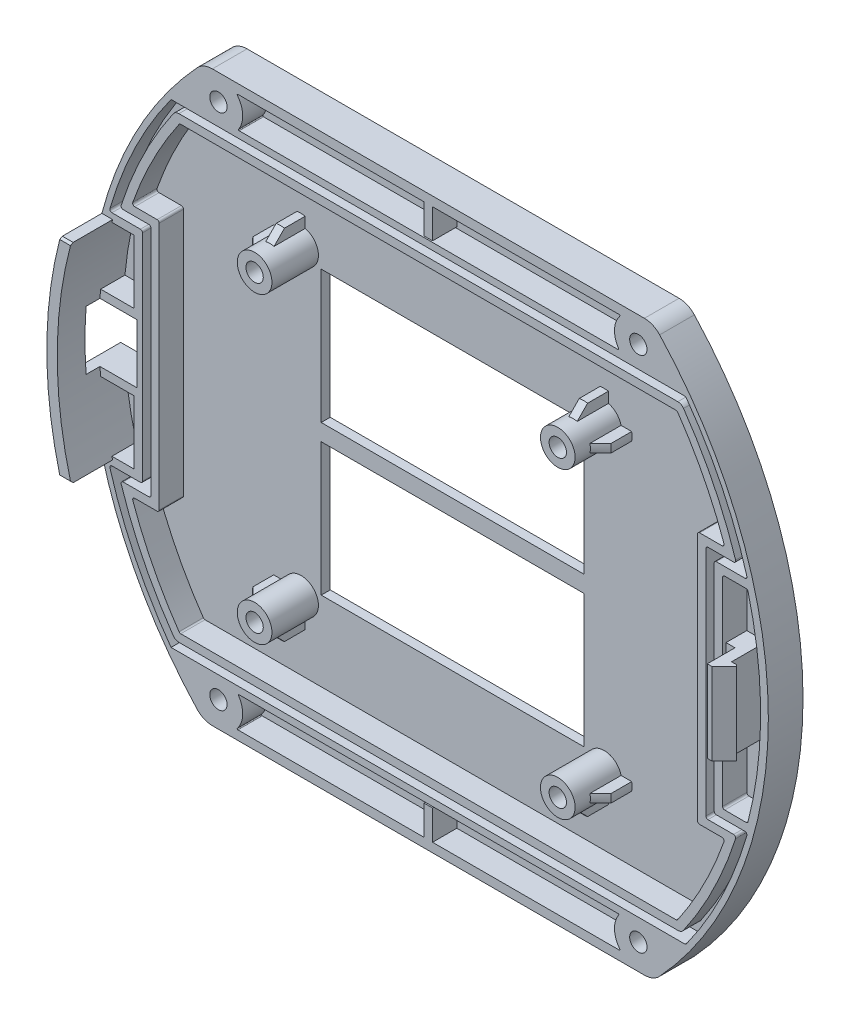
SolidWorks part; units mm, degrees
ref_plane "Front Plane" through (0, 0, 0) normal (0, 0, 1) x (1, 0, 0)
ref_plane "Top Plane" through (0, 0, 0) normal (0, 1, 0) x (1, 0, 0)
ref_plane "Right Plane" through (0, 0, 0) normal (1, 0, 0) x (0, 0, -1)
sketch "Sketch1" plane through (0, 0, 0) normal (0, 0, 1) x (1, 0, 0)
  line L0 (0, 35) -> (0, -35) construction
  line L7 (-37.5, -35) -> (37.5, -35)
  line L8 (37.5, 35) -> (-37.5, 35)
  line L10 (37.5, 35) -> (37.5, -35) construction
  line L11 (-37.5, 35) -> (-37.5, -35) construction
  arc A4 (-37.5, 35) -> (-37.5, -35) centre (10, 0) ccw
  arc A5 (37.5, 35) -> (37.5, -35) centre (-10, 0) cw
  point P17 (10, 0)
  dimension "D2" = 75
extrude "Boss-Extrude1" add sketch "Sketch1" along normal blind 5
sketch "Sketch2" plane through (0, 0, 5) normal (0, 0, 1) x (1, 0, 0)
  line L0 (-49.0021, 0) -> (49.0021, 0) construction
  line L1 (-42.635, 0) -> (-42.635, -15) construction
  line L2 (-42.635, 0) -> (-42.635, 15) construction
  line L3 (-45.5112, 15) -> (-47.0636, 15)
  line L4 (-45.5112, -15) -> (-47.0636, -15)
  arc A0 (-37.5, 35) -> (-37.5, -35) centre (10, 0) ccw construction
  arc A1 (37.5, -35) -> (37.5, 35) centre (-10, 0) ccw construction
  arc A2 (-47.0636, 15) -> (-47.0636, -15) centre (10, 0) ccw
  arc A4 (-36.2924, 34.1102) -> (-36.2924, -34.1102) centre (10, 0) ccw
  arc A5 (-45.5112, 15) -> (-45.5112, -15) centre (10, 0) ccw
  dimension "D1" = 15
  dimension "D2" = 15
  dimension "D3" = 1.5
extrude "Boss-Extrude2" add sketch "Sketch2" along normal blind 6
ref_plane "Plane2" through (-42, 0, 0) normal (1, 0, 0) x (0, 0, -1)
sketch "Sketch6" plane through (-42, 0, 0) normal (1, 0, 0) x (0, 0, -1)
  line L0 (0, 0) -> (-11, 0) construction
  line L1 (-11, 15) -> (-11, -15) construction
  line L2 (-11, 0) -> (-7, 0) construction
  line L3 (-7, 0) -> (-7, 4.25)
  line L4 (-7, 0) -> (-7, -4.25)
  line L5 (-7, 4.25) -> (0, 4.25)
  line L6 (0, -35) -> (0, 35) construction
  line L7 (0, 4.25) -> (0, -4.25)
  line L8 (0, -4.25) -> (-7, -4.25)
  dimension "D1" = 4
  dimension "D2" = 4.25
  dimension "D3" = 4.25
extrude "Cut-Extrude2" cut sketch "Sketch6" against normal blind 8
sketch "Sketch8" plane through (0, 0, 5) normal (0, 0, 1) x (1, 0, 0)
  line L0 (0, 0) -> (0, 35) construction
  line L1 (37.5, 35) -> (-37.5, 35) construction
  line L2 (0, 35) -> (0, -35) construction
  line L3 (-37.5, -35) -> (37.5, -35) construction
  line L4 (0, 0) -> (49.0021, 0) construction
  line L5 (0, 0) -> (42, 0) construction
  line L6 (42, 0) -> (44, 0) construction
  line L13 (0, 0) -> (43.2, 0) construction
  line L14 (43.7, -5.9) -> (45.2, -5.9)
  line L15 (45.2, -5.9) -> (45.2, 5.9)
  line L16 (45.2, 5.9) -> (43.7, 5.9)
  line L19 (45.2, 5.9) -> (43.7, 5.9) construction
  line L20 (43.7, 5.9) -> (43.7, -5.9)
  arc A0 (37.5, -35) -> (37.5, 35) centre (-10, 0) ccw construction
  point P5 (45.2, 0)
  dimension "D1" = 42
  dimension "D2" = 2
  dimension "D3" = 11.8
  dimension "D5" = 1.5
  dimension "D6" = 43.2
extrude "Boss-Extrude4" add sketch "Sketch8" along normal blind 3.5
ref_plane "Plane3" through (0, 0, 6.5) normal (0, 0, 1) x (1, 0, 0)
sketch "Sketch9" plane through (0, 0, 6.5) normal (0, 0, 1) x (1, 0, 0)
  line L0 (45.2, 5.9) -> (46.4, 5.9)
  line L1 (46.4, 5.9) -> (46.4, -5.9)
  line L2 (46.4, -5.9) -> (45.2, -5.9)
  line L3 (45.2, 5.9) -> (45.2, -5.9)
  dimension "D1" = 1.2
extrude "Boss-Extrude5" add sketch "Sketch9" along normal blind 2
chamfer "Chamfer2" distance 2 angle 45 1 edges at (46.4, 0, 8.5)
chamfer "Chamfer3" distance 0.5 angle 45 1 edges at (46.4, 0, 6.5)
sketch "Sketch10" plane through (0, 0, 0) normal (0, 0, 1) x (1, 0, 0)
  line L0 (-32.4294, 41) -> (32.4294, 41)
  line L1 (-37.5, 35) -> (37.5, 35)
  line L2 (-32.4294, -41) -> (32.4294, -41)
  line L3 (-37.5, -35) -> (37.5, -35)
  line L4 (0, 41) -> (0, -41) construction
  line L5 (-10, 0) -> (10, 0) construction
  arc A0 (-37.5, 35) -> (-32.4294, 41) centre (10, 0) cw
  arc A1 (37.5, 35) -> (32.4294, 41) centre (-10, 0) ccw
  arc A2 (-37.5, -35) -> (-32.4294, -41) centre (10, 0) ccw
  arc A3 (37.5, -35) -> (32.4294, -41) centre (-10, 0) cw
extrude "Boss-Extrude6" add sketch "Sketch10" along normal blind 5
sketch "Sketch11" plane through (0, 0, 5) normal (0, 0, 1) x (1, 0, 0)
  line L0 (-41.2021, 0) -> (42.0021, 0) construction
  line L1 (0, 41) -> (0, -41) construction
  circle A0 centre (-30.2641, -37.3072) radius 1.25
  circle A1 centre (30.2641, -37.3072) radius 1.25
  circle A2 centre (30.2641, 37.3072) radius 1.25
  circle A3 centre (-30.2641, 37.3072) radius 1.25
extrude "Cut-Extrude3" cut sketch "Sketch11" against normal blind 5
sketch "Sketch12" plane through (0, 0, 0) normal (0, 0, -1) x (-1, 0, 0)
  circle A0 centre (-30.2641, 37.3072) radius 3
  circle A1 centre (30.2641, 37.3072) radius 3
  circle A2 centre (30.2641, -37.3072) radius 3
  circle A3 centre (-30.2641, -37.3072) radius 3
  dimension "D1" = 6
  dimension "D2" = 6
  dimension "D3" = 6
  dimension "D4" = 6
extrude "Cut-Extrude4" cut sketch "Sketch12" against normal blind 2.5
sketch "Sketch13" plane through (0, 0, 5) normal (0, 0, 1) x (1, 0, 0)
  line L0 (-46.0165, 15.8) -> (-41.2021, 15.8)
  line L1 (-41.2021, 15.8) -> (-41.2021, -15.8)
  line L2 (-41.2021, -15.8) -> (-46.0165, -15.8)
  line L3 (-37.094, -34.2) -> (37.094, -34.2)
  line L4 (46.0165, -15.8) -> (41.2021, -15.8)
  line L5 (41.2021, -15.8) -> (41.2021, 15.8)
  line L6 (41.2021, 15.8) -> (46.0165, 15.8)
  line L7 (37.094, 34.2) -> (-37.094, 34.2)
  line L8 (10, 0) -> (-10, 0) construction
  line L9 (0, 34.2) -> (0, -34.2) construction
  line L10 (-44.4081, 17) -> (-40.0021, 17)
  line L11 (-35.9591, 33) -> (35.9591, 33)
  line L12 (-40.0021, 17) -> (-40.0021, -17)
  line L13 (44.4081, 17) -> (40.0021, 17)
  line L14 (40.0021, 17) -> (40.0021, -17)
  line L15 (44.4081, -17) -> (40.0021, -17)
  line L16 (-35.9591, -33) -> (35.9591, -33)
  line L17 (-44.4081, -17) -> (-40.0021, -17)
  line L18 (0, 33) -> (0, -33) construction
  arc A0 (-37.094, 34.2) -> (-46.0165, 15.8) centre (10, 0) ccw
  arc A1 (-46.0165, -15.8) -> (-37.094, -34.2) centre (10, 0) ccw
  arc A2 (37.094, -34.2) -> (46.0165, -15.8) centre (-10, 0) ccw
  arc A3 (46.0165, 15.8) -> (37.094, 34.2) centre (-10, 0) ccw
  arc A4 (-36.7797, 32.5714) -> (-44.4081, 17) centre (10, 0) ccw
  arc A5 (-36.7797, 32.5714) -> (-35.9591, 33) centre (-35.9591, 32) cw
  arc A6 (36.7797, 32.5714) -> (35.9591, 33) centre (35.9591, 32) ccw
  arc A7 (36.7797, 32.5714) -> (44.4081, 17) centre (-10, 0) cw
  arc A8 (36.7797, -32.5714) -> (44.4081, -17) centre (-10, 0) ccw
  arc A9 (36.7797, -32.5714) -> (35.9591, -33) centre (35.9591, -32) cw
  arc A10 (-36.7797, -32.5714) -> (-35.9591, -33) centre (-35.9591, -32) ccw
  arc A11 (-36.7797, -32.5714) -> (-44.4081, -17) centre (10, 0) cw
  point P23 (0, 33)
  point P28 (40.0021, 0)
  point P42 (-40.0021, 0)
  point P45 (0, 0)
extrude "Cut-Extrude6" cut sketch "Sketch13" against normal blind 2.5
sketch "Sketch14" plane through (0, 0, 5) normal (0, 0, 1) x (1, 0, 0)
  line L16 (-42.7507, 18.2) -> (-38.8021, 18.2)
  line L17 (-38.8021, 18.2) -> (-38.8021, -18.2)
  line L18 (-38.8021, -18.2) -> (-42.7507, -18.2)
  line L19 (-35.8545, -31.8) -> (35.8545, -31.8)
  line L20 (42.7507, -18.2) -> (38.8021, -18.2)
  line L21 (38.8021, -18.2) -> (38.8021, 18.2)
  line L22 (38.8021, 18.2) -> (42.7507, 18.2)
  line L23 (35.8545, 31.8) -> (-35.8545, 31.8)
  line L24 (-42.7507, 18.2) -> (-38.8021, 18.2)
  line L25 (-38.8021, 18.2) -> (-38.8021, -18.2)
  line L26 (-38.8021, -18.2) -> (-42.7507, -18.2)
  line L27 (-35.8545, -31.8) -> (35.8545, -31.8)
  line L28 (42.7507, -18.2) -> (38.8021, -18.2)
  line L29 (38.8021, -18.2) -> (38.8021, 18.2)
  line L30 (38.8021, 18.2) -> (42.7507, 18.2)
  line L31 (35.8545, 31.8) -> (-35.8545, 31.8)
  arc A16 (-35.8545, 31.8) -> (-42.7507, 18.2) centre (10, 0) ccw
  arc A17 (-42.7507, -18.2) -> (-35.8545, -31.8) centre (10, 0) ccw
  arc A18 (35.8545, -31.8) -> (42.7507, -18.2) centre (-10, 0) ccw
  arc A19 (42.7507, 18.2) -> (35.8545, 31.8) centre (-10, 0) ccw
  arc A20 (-35.8545, 31.8) -> (-42.7507, 18.2) centre (10, 0) ccw
  arc A21 (-42.7507, -18.2) -> (-35.8545, -31.8) centre (10, 0) ccw
  arc A22 (35.8545, -31.8) -> (42.7507, -18.2) centre (-10, 0) ccw
  arc A23 (42.7507, 18.2) -> (35.8545, 31.8) centre (-10, 0) ccw
  dimension "D1" = 1.2
extrude "Cut-Extrude7" cut sketch "Sketch14" against normal blind 3.5
sketch "Sketch15" plane through (0, 0, 5) normal (0, 0, 1) x (1, 0, 0)
  line L0 (0.031, 41) -> (0.031, -41) construction
  line L1 (-40.0021, -0.0076) -> (42.0021, -0.0076) construction
  line L2 (27.5192, -39.6767) -> (-27.4573, -39.6767)
  line L3 (-27.2755, 35.2002) -> (27.3374, 35.2002)
  line L4 (-27.2831, -35.2042) -> (27.345, -35.2042)
  line L5 (27.5155, 39.6568) -> (-27.4535, 39.6568)
  arc A12 (-27.5316, 39.4943) -> (-27.3585, 35.356) centre (-30.2641, 37.3072) cw
  arc A13 (27.5935, 39.4943) -> (27.4204, 35.356) centre (30.326, 37.3072) ccw
  arc A14 (27.5972, -39.5141) -> (27.4278, -35.3603) centre (30.326, -37.3225) cw
  arc A15 (-27.5352, -39.5141) -> (-27.3659, -35.3603) centre (-30.2641, -37.3225) ccw
  arc A16 (-27.2755, 35.2002) -> (-27.3585, 35.356) centre (-27.2755, 35.3002) cw
  arc A17 (-27.5316, 39.4943) -> (-27.4535, 39.6568) centre (-27.4535, 39.5568) cw
  arc A18 (27.4278, -35.3603) -> (27.345, -35.2042) centre (27.345, -35.3042) ccw
  arc A19 (27.3374, 35.2002) -> (27.4204, 35.356) centre (27.3374, 35.3002) ccw
  arc A20 (27.5935, 39.4943) -> (27.5155, 39.6568) centre (27.5155, 39.5568) ccw
  arc A21 (27.5192, -39.6767) -> (27.5972, -39.5141) centre (27.5192, -39.5767) ccw
  arc A22 (-27.3659, -35.3603) -> (-27.2831, -35.2042) centre (-27.2831, -35.3042) cw
  arc A23 (-27.5352, -39.5141) -> (-27.4573, -39.6767) centre (-27.4573, -39.5767) ccw
  point P14 (0.031, -39.6767)
  point P20 (0.031, -35.2042)
  dimension "D1" = 3.5
  dimension "D2" = 0.1
  dimension "D3" = 0.1
  dimension "D4" = 0.1
  dimension "D5" = 0.1
  dimension "D6" = 0.1
extrude "Cut-Extrude8" cut sketch "Sketch15" against normal blind 3.5
sketch "Sketch16" plane through (0, 0, 5) normal (0, 0, 1) x (1, 0, 0)
  line L2 (42.4021, -15.8) -> (42.4021, 15.8)
  line L3 (42.4021, -14.6) -> (42.4021, 14.6)
  line L5 (41.2021, 14.6) -> (46.0165, 14.6)
  line L6 (42.4021, 14.6) -> (46.0165, 14.6)
  line L8 (46.0165, -14.6) -> (41.2021, -14.6)
  line L9 (46.0165, -14.6) -> (42.4021, -14.6)
  line L19 (43.7, 5.9) -> (45.2, 5.9)
  line L20 (45.2, 5.9) -> (43.7, 5.9) construction
  line L21 (45.2, 5.9) -> (45.2, -5.9)
  line L22 (45.2, -5.9) -> (43.7, -5.9)
  line L23 (43.7, -5.9) -> (43.7, 5.9)
  arc A0 (46.0165, -14.6) -> (46.0165, 14.6) centre (-10, 0) ccw
  arc A1 (46.0165, 15.8) -> (37.094, 34.2) centre (-10, 0) ccw construction
  point P18 (45.2, -5.9)
  point P19 (0, 0)
  point P20 (0, 0)
  dimension "D1" = 1.2
  dimension "D2" = 1.2
  dimension "D3" = 1.2
extrude "Cut-Extrude10" cut sketch "Sketch16" against normal blind 3.5
sketch "Sketch17" plane through (0, 0, 1.5) normal (0, 0, 1) x (1, 0, 0)
  line L0 (43.7, 5.9) -> (42.4021, 5.9)
  line L1 (42.4021, 14.6) -> (42.4021, -14.6) construction
  line L2 (42.4021, 5.9) -> (42.4021, -5.9)
  line L3 (42.4021, 14.6) -> (42.4021, -14.6) construction
  line L4 (42.4021, -5.9) -> (43.7, -5.9)
  line L5 (43.7, -5.9) -> (43.7, 5.9)
extrude "Boss-Extrude7" add sketch "Sketch17" along normal blind 3
sketch "Sketch19" plane through (0, 0, 1.5) normal (0, 0, 1) x (1, 0, 0)
  line L0 (0, -39.8) -> (0, 39.8) construction
  line L1 (-41.2021, 0) -> (41.2021, -0.15) construction
  line L2 (0.6, -35.4) -> (0.6, -39.8)
  line L3 (0.6, -39.8) -> (-0.6, -39.8)
  line L4 (-0.6, -39.8) -> (-0.6, -35.4)
  line L5 (-0.6, -35.4) -> (0.6, -35.4)
  line L6 (-0.6, 35.4) -> (-0.6, 39.8)
  line L7 (-0.6, 39.8) -> (0.6, 39.8)
  line L8 (0.6, 39.8) -> (0.6, 35.4)
  line L9 (0.6, 35.4) -> (-0.6, 35.4)
extrude "Boss-Extrude8" add sketch "Sketch19" along normal blind 3.5
chamfer "Chamfer4" distance 0.3 angle 45 1 edges at (-46.2874, -15, 11)
chamfer "Chamfer5" distance 0.3 angle 45 1 edges at (-46.2874, 15, 11)
chamfer "Chamfer8" distance 0.5 angle 45 2 edges at (-45.4244, 4.25, 0) (-45.4244, -4.25, 0)
sketch "Sketch21" plane through (0, 0, 5) normal (0, 0, 1) x (1, 0, 0)
  line L2 (-41.2021, -14.6) -> (-46.0165, -14.6)
  line L3 (-42.4021, -14.6) -> (-45.6177, -14.6)
  line L5 (-47.3448, -5.45) -> (-42, -5.45)
  line L6 (-47.2433, -5.45) -> (-42.4021, -5.45)
  line L8 (-42.4021, 15.8) -> (-42.4021, -15.8)
  line L9 (-42.4021, 14.6) -> (-42.4021, 5.45)
  line L11 (-42, 5.45) -> (-47.3448, 5.45)
  line L12 (-42.4021, 5.45) -> (-47.2433, 5.45)
  line L13 (-42.4021, -5.45) -> (-42.4021, -14.6)
  line L14 (-46.0165, 14.6) -> (-41.2021, 14.6)
  line L15 (-45.6177, 14.6) -> (-42.4021, 14.6)
  arc A2 (-47.3448, -4.25) -> (-45.5112, -15) centre (10, 0) ccw
  arc A3 (-47.2433, -5.45) -> (-45.6177, -14.6) centre (10, 0) ccw
  arc A5 (-45.5112, 15) -> (-47.3448, 4.25) centre (10, 0) ccw
  arc A6 (-45.6177, 14.6) -> (-47.2433, 5.45) centre (10, 0) ccw
  dimension "D1" = 0
  dimension "D2" = 0
  dimension "D3" = 1.2
  dimension "D4" = 1.2
  dimension "D5" = 1.2
  dimension "D6" = 1.2
  dimension "D7" = 1.2
extrude "Cut-Extrude11" cut sketch "Sketch21" against normal blind 3.5
sketch "Sketch22" plane through (0, 0, 1.5) normal (0, 0, 1) x (1, 0, 0)
  line L0 (-38.8021, 0) -> (38.8021, 0) construction
  line L1 (-21.85, 21.85) -> (-21.85, -21.85) construction
  line L2 (-21.85, -21.85) -> (21.85, -21.85) construction
  line L3 (-38.8021, 18.2) -> (-38.8021, -18.2) construction
  line L4 (38.8021, -18.2) -> (38.8021, 18.2) construction
  line L5 (0, 31.8) -> (0, -31.8) construction
  line L6 (35.8545, 31.8) -> (-35.8545, 31.8) construction
  line L7 (-35.8545, -31.8) -> (35.8545, -31.8) construction
  circle A0 centre (-21.85, 21.85) radius 1.25
  circle A1 centre (-21.85, 21.85) radius 2.5
  circle A2 centre (-21.85, -21.85) radius 1.25
  circle A3 centre (-21.85, -21.85) radius 2.5
  circle A4 centre (21.85, -21.85) radius 1.25
  circle A5 centre (21.85, -21.85) radius 2.5
  circle A6 centre (21.85, 21.85) radius 2.5
  circle A7 centre (21.85, 21.85) radius 1.25
  point P14 (-21.85, 0)
  point P16 (0, -21.85)
  point P21 (0, 0)
  dimension "D3" = 2.5
  dimension "D4" = 5
  dimension "D5" = 2.5
  dimension "D6" = 5
  dimension "D1" = 43.7
  dimension "D2" = 43.7
extrude "Boss-Extrude9" add sketch "Sketch22" along normal blind 6.7
sketch "Sketch23" plane through (0, 0, 1.5) normal (0, 0, 1) x (1, 0, 0)
  line L0 (0, 31.8) -> (0, -31.8) construction
  line L1 (35.8545, 31.8) -> (-35.8545, 31.8) construction
  line L2 (-35.8545, -31.8) -> (35.8545, -31.8) construction
  line L3 (-38.8021, 0) -> (38.8021, 0) construction
  line L4 (-38.8021, 18.2) -> (-38.8021, -18.2) construction
  line L5 (38.8021, -18.2) -> (38.8021, 18.2) construction
  line L6 (-21.85, 21.85) -> (-21.85, 26.4502) construction
  line L7 (-21.25, 24.2769) -> (-21.25, 25.8047)
  line L8 (-22.45, 24.2769) -> (-22.45, 25.8047)
  line L9 (-21.85, 21.85) -> (-26.9377, 21.85) construction
  line L10 (-22.45, 21.85) -> (-22.45, 26.4502) construction
  line L11 (-21.25, 21.85) -> (-21.25, 26.4502) construction
  line L12 (-21.85, 21.85) -> (-25.1057, 25.1057) construction
  line L13 (-24.2769, 22.45) -> (-25.8047, 22.45)
  line L14 (-24.2769, 21.25) -> (-25.8047, 21.25)
  line L15 (-24.2769, -21.25) -> (-25.8047, -21.25)
  line L16 (-24.2769, -22.45) -> (-25.8047, -22.45)
  line L17 (-22.45, -24.2769) -> (-22.45, -25.8047)
  line L18 (-21.25, -24.2769) -> (-21.25, -25.8047)
  line L19 (21.25, -24.2769) -> (21.25, -25.8047)
  line L20 (22.45, -24.2769) -> (22.45, -25.8047)
  line L21 (24.2769, -22.45) -> (25.8047, -22.45)
  line L22 (24.2769, -21.25) -> (25.8047, -21.25)
  line L23 (24.2769, 21.25) -> (25.8047, 21.25)
  line L24 (24.2769, 22.45) -> (25.8047, 22.45)
  line L25 (22.45, 24.2769) -> (22.45, 25.8047)
  line L26 (21.25, 24.2769) -> (21.25, 25.8047)
  arc A0 (-21.25, 24.2769) -> (-22.45, 24.2769) centre (-21.85, 21.85) ccw
  arc A3 (-22.45, 25.8047) -> (-21.25, 25.8047) centre (-21.85, 21.85) cw
  arc A4 (-24.2769, 21.25) -> (-24.2769, 22.45) centre (-21.85, 21.85) cw
  arc A5 (-25.8047, 22.45) -> (-25.8047, 21.25) centre (-21.85, 21.85) ccw
  arc A6 (-25.8047, -22.45) -> (-25.8047, -21.25) centre (-21.85, -21.85) cw
  arc A7 (-24.2769, -21.25) -> (-24.2769, -22.45) centre (-21.85, -21.85) ccw
  arc A8 (-21.25, -24.2769) -> (-22.45, -24.2769) centre (-21.85, -21.85) cw
  arc A9 (-22.45, -25.8047) -> (-21.25, -25.8047) centre (-21.85, -21.85) ccw
  arc A10 (22.45, -25.8047) -> (21.25, -25.8047) centre (21.85, -21.85) cw
  arc A11 (21.25, -24.2769) -> (22.45, -24.2769) centre (21.85, -21.85) ccw
  arc A12 (24.2769, -21.25) -> (24.2769, -22.45) centre (21.85, -21.85) cw
  arc A13 (25.8047, -22.45) -> (25.8047, -21.25) centre (21.85, -21.85) ccw
  arc A14 (25.8047, 22.45) -> (25.8047, 21.25) centre (21.85, 21.85) cw
  arc A15 (24.2769, 21.25) -> (24.2769, 22.45) centre (21.85, 21.85) ccw
  arc A16 (21.25, 24.2769) -> (22.45, 24.2769) centre (21.85, 21.85) cw
  arc A17 (22.45, 25.8047) -> (21.25, 25.8047) centre (21.85, 21.85) ccw
  dimension "D1" = 1.5
  dimension "D4" = 45
  dimension "D2" = 0.6
  dimension "D3" = 0.6
extrude "Boss-Extrude10" add sketch "Sketch23" along normal blind 5
chamfer "Chamfer9" distance 2 angle 45 8 edges at (-25.85, 21.85, 6.5) (-21.85, 25.85, 6.5) (21.85, 25.85, 6.5) (25.85, 21.85, 6.5) (25.85, -21.85, 6.5) (21.85, -25.85, 6.5) (-21.85, -25.85, 6.5) (-25.85, -21.85, 6.5)
sketch "Sketch24" plane through (0, 0, 1.5) normal (0, 0, 1) x (1, 0, 0)
  line L0 (-21.85, -21.85) -> (21.85, -21.85) construction
  line L1 (21.85, -21.85) -> (21.85, 21.85) construction
  line L2 (21.85, 21.85) -> (-21.85, 21.85) construction
  line L3 (-21.85, 21.85) -> (-21.85, -21.85) construction
  line L4 (0, -21.85) -> (0, 21.85) construction
  line L5 (-21.85, 0) -> (21.85, 0) construction
  line L6 (21.85, 20.35) -> (-21.85, 20.35) construction
  line L7 (18.95, -21.85) -> (18.95, 21.85) construction
  line L8 (-21.85, -20.35) -> (21.85, -20.35) construction
  line L9 (-21.85, -1.2) -> (21.85, -1.2) construction
  line L10 (-18.95, -21.85) -> (-18.95, 21.85) construction
  line L11 (-21.85, 1.2) -> (21.85, 1.2) construction
  line L12 (0, -1.2) -> (-18.95, -1.2)
  line L13 (-18.95, -1.2) -> (-18.95, -20.35)
  line L14 (-18.95, -20.35) -> (18.95, -20.35)
  line L15 (18.95, -20.35) -> (18.95, -1.2)
  line L16 (18.95, -1.2) -> (0, -1.2)
  line L18 (-18.95, 1.2) -> (-18.95, 20.35)
  line L19 (-18.95, 20.35) -> (18.95, 20.35)
  line L20 (18.95, 20.35) -> (18.95, 1.2)
  line L21 (18.95, 1.2) -> (-18.95, 1.2)
  dimension "D1" = 1.5
  dimension "D2" = 2.9
  dimension "D3" = 1.5
  dimension "D4" = 1.2
  dimension "D5" = 1.2
extrude "Cut-Extrude12" cut sketch "Sketch24" against normal blind 1.5
sketch "Sketch26" plane through (0, 0, 0) normal (0, 0, -1) x (-1, 0, 0)
  line L0 (0, 41) -> (0, -41) construction
  line L1 (-32.4294, 41) -> (32.4294, 41) construction
  line L2 (32.4294, -41) -> (-32.4294, -41) construction
  line L3 (-49.0021, 0) -> (42, 0) construction
  line L4 (42, -4.75) -> (42, 4.75) construction
  line L5 (0, 0) -> (0, 25) construction
  line L6 (0, 25) -> (-25, 25)
  line L7 (0, 25) -> (25, 25)
  line L8 (-25, 25) -> (-25, -25)
  line L9 (-25, -25) -> (25, -25)
  line L10 (25, -25) -> (25, 25)
  arc A0 (-32.4294, 41) -> (-32.4294, -41) centre (10, 0) ccw construction
  dimension "D1" = 25
  dimension "D2" = 25
  dimension "D3" = 25
  dimension "D4" = 50
  dimension "D5" = 50
extrude "Cut-Extrude13" cut sketch "Sketch26" against normal blind 0.2
fillet "Fillet1" radius 2 1 edges at (25, 25, 0.1)
fillet "Fillet2" radius 2 1 edges at (-25, 25, 0.1)
fillet "Fillet3" radius 2 1 edges at (-25, -25, 0.1)
fillet "Fillet4" radius 2 1 edges at (25, -25, 0.1)
fillet "Fillet5" radius 3 4 edges at (-32.4294, 41, 2.5) (-32.4294, -41, 2.5) (32.4294, -41, 2.5) (32.4294, 41, 2.5)
fillet "Fillet6" radius 0.3 1 edges at (-44.4081, -17, 3.75)
fillet "Fillet7" radius 0.3 1 edges at (-46.0165, -15.8, 3.75)
fillet "Fillet8" radius 0.3 1 edges at (-41.2021, -15.8, 3.75)
fillet "Fillet9" radius 0.3 1 edges at (-40.0021, -17, 3.75)
fillet "Fillet10" radius 0.3 1 edges at (-40.0021, 17, 3.75)
fillet "Fillet11" radius 0.3 1 edges at (-41.2021, 15.8, 3.75)
fillet "Fillet13" radius 0.3 1 edges at (-46.0165, 15.8, 3.75)
fillet "Fillet14" radius 0.3 1 edges at (-44.4081, 17, 3.75)
fillet "Fillet15" radius 0.3 1 edges at (-42.7507, 18.2, 3.25)
fillet "Fillet16" radius 0.3 1 edges at (-38.8021, 18.2, 3.25)
fillet "Fillet17" radius 0.3 1 edges at (-35.8545, 31.8, 3.25)
fillet "Fillet18" radius 0.3 1 edges at (-38.8021, -18.2, 3.25)
fillet "Fillet19" radius 0.3 1 edges at (-42.7507, -18.2, 3.25)
fillet "Fillet20" radius 0.3 1 edges at (-35.8545, -31.8, 3.25)
fillet "Fillet21" radius 0.3 1 edges at (35.8545, -31.8, 3.25)
fillet "Fillet22" radius 0.3 2 edges at (38.8021, -18.2, 3.25) (42.7507, -18.2, 3.25)
fillet "Fillet23" radius 0.3 1 edges at (44.4081, -17, 3.75)
fillet "Fillet24" radius 0.3 1 edges at (40.0021, -17, 3.75)
fillet "Fillet26" radius 0.3 1 edges at (38.8021, 18.2, 3.25)
fillet "Fillet27" radius 0.3 1 edges at (41.2021, 15.8, 3.75)
fillet "Fillet28" radius 0.3 1 edges at (42.7507, 18.2, 3.25)
fillet "Fillet29" radius 0.3 1 edges at (40.0021, 17, 3.75)
fillet "Fillet30" radius 0.3 1 edges at (44.4081, 17, 3.75)
fillet "Fillet31" radius 0.3 1 edges at (35.8545, 31.8, 3.25)
fillet "Fillet32" radius 0.3 1 edges at (46.0165, 15.8, 3.75)
fillet "Fillet33" radius 0.3 1 edges at (46.0165, -15.8, 3.75)
fillet "Fillet34" radius 0.3 1 edges at (41.2021, -15.8, 3.75)
fillet "Fillet35" radius 0.3 1 edges at (42.4021, -14.6, 3.25)
fillet "Fillet36" radius 0.3 1 edges at (46.0165, -14.6, 3.25)
fillet "Fillet37" radius 0.3 1 edges at (42.4021, 14.6, 3.25)
fillet "Fillet38" radius 0.3 1 edges at (46.0165, 14.6, 3.25)
fillet "Fillet39" radius 0.3 1 edges at (37.094, -34.2, 3.75)
fillet "Fillet40" radius 0.3 1 edges at (37.094, 34.2, 3.75)
fillet "Fillet42" radius 0.5 1 edges at (-33.2641, -37.3072, 0)
fillet "Fillet43" radius 0.5 1 edges at (-33.2641, 37.3072, 0)
fillet "Fillet44" radius 0.5 1 edges at (27.2641, 37.3072, 0)
fillet "Fillet45" radius 0.5 1 edges at (27.2641, -37.3072, 0)
